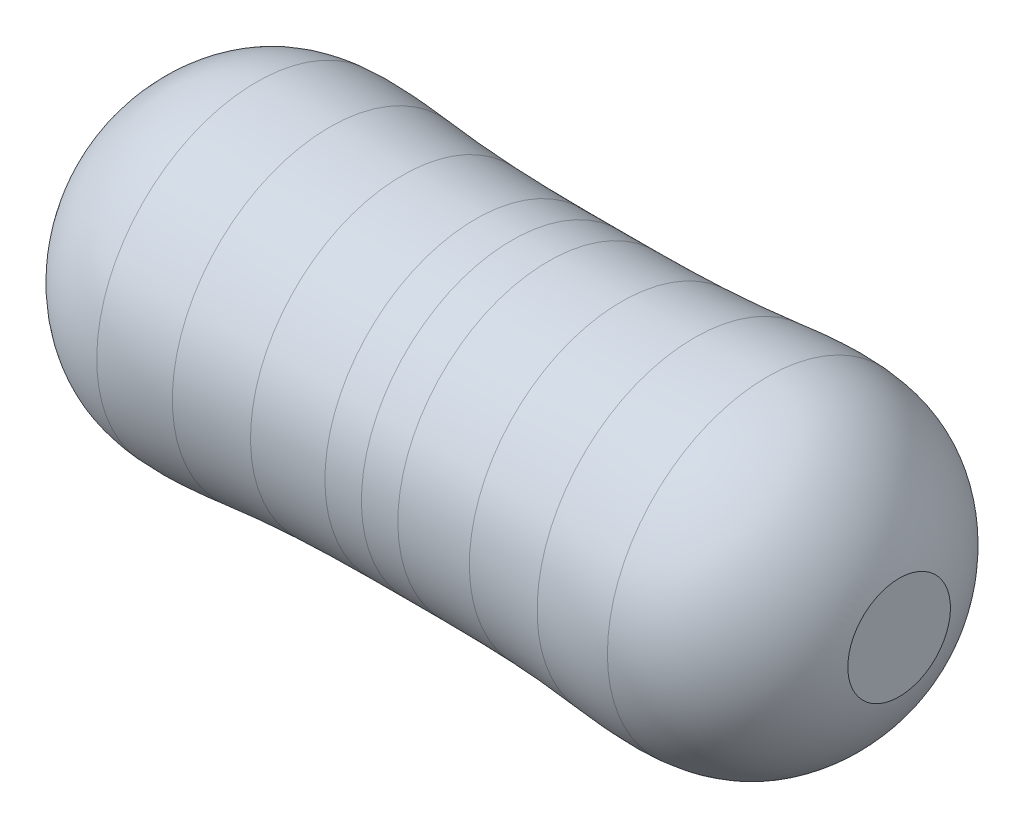
SolidWorks part; units mm, degrees
ref_plane "Front Plane" through (0, 0, 0) normal (0, 0, 1) x (1, 0, 0)
ref_plane "Top Plane" through (0, 0, 0) normal (0, 1, 0) x (1, 0, 0)
ref_plane "Right Plane" through (0, 0, 0) normal (1, 0, 0) x (0, 0, -1)
sketch "Sketch1" plane through (0, 0, 0) normal (0, 0, 1) x (1, 0, 0)
  line L0 (0, -2.54) -> (0, 1.016)
  arc A0 (0, 1.016) -> (0.762, 1.778) centre (0.762, 1.016) cw
ref_plane "Plane4" through (0, -2.54, 0) normal (0, 1, 0) x (-1, 0, 0)
sketch "Sketch3" plane through (0, -2.54, 0) normal (0, 1, 0) x (-1, 0, 0)
  circle A0 centre (0, 0) radius 0.3048
  dimension "D1" = 0.6096
sweep "Base-Sweep" add profiles "Sketch3" path "Sketch1"
sketch "Sketch4" plane through (0, 0, 0) normal (0, 0, 1) x (1, 0, 0)
  line L0 (0.762, 1.778) -> (5.0546, 1.778) construction
  line L2 (5.0546, 3.429) -> (5.0546, 1.778)
  line L3 (5.0546, 1.778) -> (0.762, 1.778)
  spline S0 degree 3 poles (0.762, 1.778) (0.7578, 1.8794) (0.7319, 2.5038) (1.5817, 3.7123) (3.3609, 3.4282) (4.4792, 3.4287) (5.0546, 3.429) knots 0 0 0 0 0.05769 0.355059 0.66814 1 1 1 1
revolve "Boss-Revolve1" add sketch "Sketch4" angle 360 about L0
sketch "Sketch6" plane through (0, 0, 0) normal (0, 1, 0) x (1, 0, 0)
  line L2 (5.0546, -1.651) -> (5.0546, 1.651) construction
  line L10 (3.8546, 2.8448) -> (3.8546, -5.424)
  line L11 (4.6546, -5.424) -> (3.8546, -5.424)
  line L12 (4.6546, 2.8448) -> (4.6546, -5.424)
  line L13 (4.6546, 2.8448) -> (3.8546, 2.8448)
  dimension "D1" = 0.8
  dimension "D2" = 0.4
split line "band 1"
mirror "Boss-Mirror1" about plane through (5.0546, 3.429, 0) normal (1, 0, 0) of bodies 102
sketch "Sketch7" plane through (0, 0, 0) normal (0, 1, 0) x (1, 0, 0)
  line L1 (2.2546, 2.5146) -> (3.0546, 2.5146)
  line L2 (2.2546, 2.5146) -> (2.2546, -2.7686)
  line L3 (2.2546, -2.7686) -> (3.0546, -2.7686)
  line L4 (3.0546, 2.5146) -> (3.0546, -2.7686)
  line L5 (3.8546, -1.6674) -> (3.8546, 1.6674) construction
  dimension "D1" = 0.8
  dimension "D2" = 0.8
split line "band 2"
ref_plane "Plane5" through (0, -0.381, 0) normal (0, 1, 0) x (-1, 0, 0)
sketch "Component_Outline" plane through (0, -0.381, 0) normal (0, 1, 0) x (-1, 0, 0)
  line L1 (-9.3472, 0.3048) -> (-9.3472, -0.3048) construction
  line L3 (-0.762, 0.3048) -> (0, 0.3048)
  line L4 (0, 0.3048) -> (-0.762, 0.3048) construction
  line L5 (-0.762, -0.3048) -> (0, -0.3048)
  line L6 (-9.3472, 0.3048) -> (-10.1092, 0.3048)
  line L7 (-10.1092, -0.3048) -> (-9.3472, -0.3048)
  line L8 (-0.762, -0.3048) -> (-0.762, -1.7709)
  line L9 (-0.762, 1.776) -> (-9.3472, 1.776)
  line L10 (-0.762, 1.776) -> (-0.762, 0.3048)
  line L11 (-0.762, -1.7709) -> (-9.3472, -1.7709)
  line L12 (-9.3472, 1.776) -> (-9.3472, 0.3048)
  line L13 (-9.3472, -0.3048) -> (-9.3472, -1.7709)
  circle A0 centre (0, 0) radius 0.3048 construction
  arc A1 (0, 0.3048) -> (0, -0.3048) centre (0, 0) cw
  arc A2 (-10.1092, 0.3048) -> (-10.1092, -0.3048) centre (-10.1092, 0) ccw
  circle A3 centre (-10.1092, 0) radius 0.3048 construction
  spline S1 degree 3 poles (-0.762, 0.3048) (-0.8053, 0.8301) (-1.3364, 1.5854) (-2.0434, 1.7379) (-2.2546, 1.7537) knots 0.05769 0.05769 0.05769 0.05769 0.355059 0.475239 0.475239 0.475239 0.475239 construction
  spline S2 degree 3 poles (-7.8546, 1.7537) (-8.0658, 1.7379) (-8.7728, 1.5854) (-9.3039, 0.8301) (-9.3472, 0.3048) knots 0.524761 0.524761 0.524761 0.524761 0.644941 0.94231 0.94231 0.94231 0.94231 construction
  dimension "D1" = 3.5469
  dimension "D2" = 1.4712
ref_plane "Plane6" through (0.8, 0, 0) normal (1, 0, 0) x (0, 0, -1)
sketch "Sketch8" plane through (0.8, 0, 0) normal (1, 0, 0) x (0, 0, -1)
  circle A0 centre (0, 0) radius 6.1642
extrude "Cut-Extrude1" cut sketch "Sketch8" against normal through all
ref_plane "Plane7" through (9.3, 0, 0) normal (1, 0, 0) x (0, 0, -1)
extrude "Cut-Extrude2" cut sketch "Sketch8<2>" along normal through all from surface contours A0 starting at plane "Plane7"
sketch "Sketch8<2>" plane through (0.8, 0, 0) normal (1, 0, 0) x (0, 0, -1) same geometry as "Sketch8"
